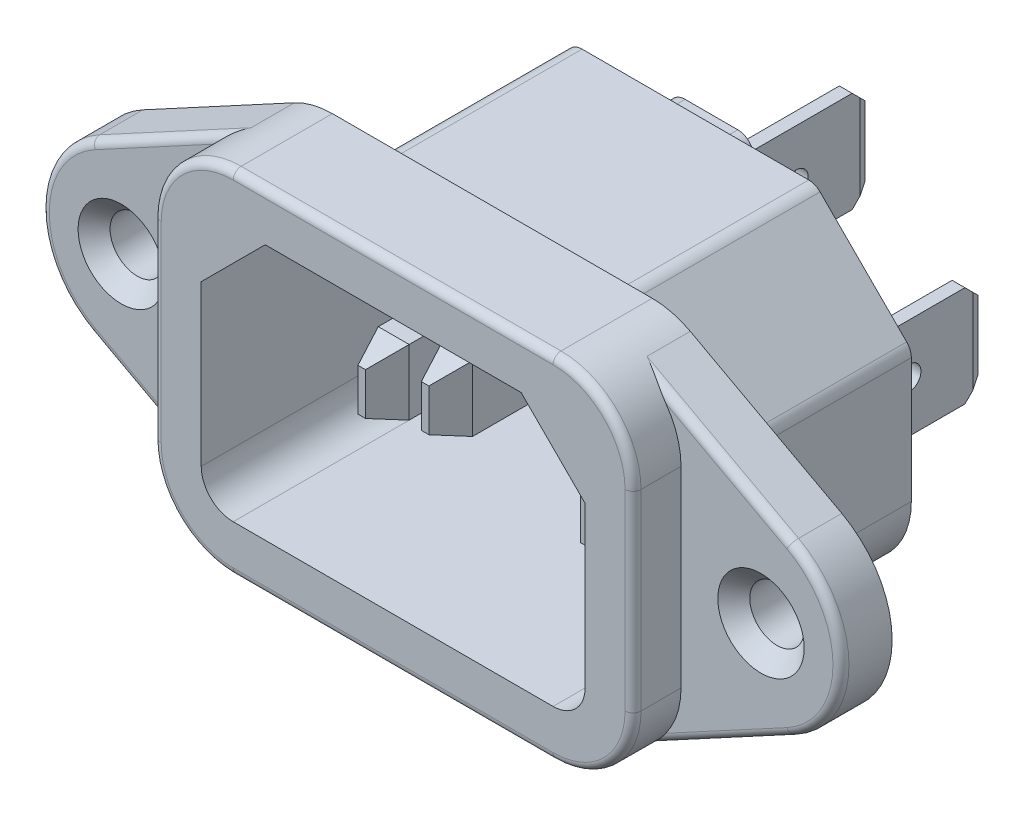
SolidWorks part; units mm, degrees
ref_plane "Front Plane" through (0, 0, 0) normal (0, 0, 1) x (1, 0, 0)
ref_plane "Top Plane" through (0, 0, 0) normal (0, 1, 0) x (1, 0, 0)
ref_plane "Right Plane" through (0, 0, 0) normal (1, 0, 0) x (0, 0, -1)
sketch "Sketch1" plane through (0, 0, 0) normal (0, 0, 1) x (1, 0, 0)
  line L0 (0, 11) -> (-10, 11)
  line L1 (-12.377, 10.3988) -> (-21.8524, 5.2786)
  line L2 (-21.8524, -5.2786) -> (-12.377, -10.3988)
  line L3 (-10, -11) -> (0, -11)
  line L4 (0, 11) -> (0, -11)
  line L5 (0, 0) -> (-19, 0) construction
  line L6 (-10, -11) -> (-10, 11) construction
  line L7 (-12.377, 10.3988) -> (-12.377, -10.3988) construction
  arc A0 (-10, 11) -> (-12.377, 10.3988) centre (-10, 6) ccw
  arc A1 (-10, -11) -> (-12.377, -10.3988) centre (-10, -6) cw
  arc A2 (-21.8524, 5.2786) -> (-21.8524, -5.2786) centre (-19, 0) ccw
  circle A3 centre (-20, 0) radius 1.7
  point P2 (0, 0)
  point P16 (-25, 0)
  dimension "D2" = 5
  dimension "D3" = 6
  dimension "D4" = 3.4
  dimension "D5" = 20
  dimension "D6" = 25
  dimension "D1" = 22
  dimension "D7" = 10
extrude "flange" add sketch "Sketch1" along normal blind 3.2
sketch "Sketch2" plane through (0, 0, 3.2) normal (0, 0, 1) x (1, 0, 0)
  line L1 (0, 11) -> (-10, 11)
  line L2 (0, 11) -> (-10, 11) construction
  line L3 (0, -11) -> (0, 11) construction
  line L4 (-15, 6) -> (-15, -6)
  line L5 (-10, -11) -> (0, -11)
  line L6 (-10, -11) -> (0, -11) construction
  arc A0 (-10, 11) -> (-15, 6) centre (-10, 6) ccw
  arc A2 (-10, -11) -> (-15, -6) centre (-10, -6) cw
  line M1 (0, -11) -> (0, 11)
  line M2 (0, 11) -> (-10, 11)
  line M8 (-10, -11) -> (0, -11)
  dimension "D1" = 5
  dimension "D2" = 15
extrude "top" add sketch "Sketch2" along normal blind 3 contours A2 A0 L4 M8 M1 M2 region at (-7.2855, 0, 3.2)
sketch "Sketch4" plane through (0, 0, 0) normal (0, 0, -1) x (-1, 0, 0)
  line L0 (0, -9.6) -> (8.5, -9.6)
  line L1 (0, -11) -> (0, 11) construction
  line L2 (13.5, -4.6) -> (13.5, 3.1858)
  line L3 (7.0858, 9.6) -> (0, 9.6)
  line L4 (13.2071, 3.8929) -> (7.7929, 9.3071)
  line L5 (0, -9.6) -> (0, 9.6)
  arc A0 (8.5, -9.6) -> (13.5, -4.6) centre (8.5, -4.6) ccw
  arc A1 (7.7929, 9.3071) -> (7.0858, 9.6) centre (7.0858, 8.6) ccw
  arc A2 (13.5, 3.1858) -> (13.2071, 3.8929) centre (12.5, 3.1858) ccw
  point P4 (13.5, 9.6)
  point P10 (0, 0)
  point P14 (7.5, 9.6)
  point P17 (13.5, 3.6)
  dimension "D3" = 5
  dimension "D4" = 1
  dimension "D1" = 19.2
  dimension "D2" = 13.5
extrude "rear" add sketch "Sketch4" along normal blind 12.7
sketch "Sketch3" plane through (0, 0, 6.2) normal (0, 0, 1) x (1, 0, 0)
  line L0 (0, -8) -> (-10, -8)
  line L1 (0, -11) -> (0, 11) construction
  line L2 (-12, -6) -> (-12, 4)
  line L3 (-12, 4) -> (-8, 8)
  line L4 (-8, 8) -> (0, 8)
  line L5 (0, 8) -> (0, -8)
  line L6 (0, 8) -> (0, -8)
  arc A0 (-10, -8) -> (-12, -6) centre (-10, -6) cw
  point P9 (0, 0)
  line M3 (0, -11) -> (0, 11)
  dimension "D3" = 2
  dimension "D1" = 12
  dimension "D2" = 16
  dimension "D4" = 12
  dimension "D5" = 135
extrude "socket" cut sketch "Sketch3" against normal blind 17 contours A0 L0 L4 L3 L2 M3 region at (-5.7701, -0.2558, 6.2)
chamfer "Chamfer2" distance 1 angle 45 1 edges at (-18.3, 0, 3.2)
mirror "Mirror1" about plane through (0, 0, 0) normal (1, 0, 0) of bodies 105
sketch "Sketch5" plane through (0, 0, -10.8) normal (0, 0, 1) x (1, 0, 0)
  line L0 (-6, -1.95) -> (6, -1.95) construction
  line L1 (-7.93, 0.1) -> (-6, 0.1)
  line L2 (-7.93, 0.1) -> (-7.93, -4)
  line L3 (-7.93, -4) -> (-6, -4)
  line L4 (-6, 0.1) -> (-6, -4)
  line L5 (0, 8) -> (0, -8) construction
  line L6 (7.93, 0.1) -> (6, 0.1)
  line L7 (7.93, 0.1) -> (7.93, -4)
  line L8 (7.93, -4) -> (6, -4)
  line L9 (6, 0.1) -> (6, -4)
  line L10 (-0.965, 4.2) -> (0.965, 4.2)
  line L11 (-0.965, 4.2) -> (-0.965, 0.1)
  line L12 (-0.965, 0.1) -> (0.965, 0.1)
  line L13 (0.965, 4.2) -> (0.965, 0.1)
  line L14 (-8, 8) -> (8, 8) construction
  line L15 (10, -8) -> (-10, -8) construction
  point P20 (0, -1.95)
  point P21 (0, 0.1)
  dimension "D1" = 1.93
  dimension "D2" = 4.1
  dimension "D3" = 12
  dimension "D4" = 6.05
extrude "pin" add sketch "Sketch5" along normal blind 12
sketch "Sketch6" plane through (0, 0, 1.2) normal (0, 0, 1) x (1, 0, 0)
  line L4 (-0.965, 4.2) -> (-0.965, 0.1)
  line L5 (-0.965, 0.1) -> (0.965, 0.1)
  line L6 (0.965, 0.1) -> (0.965, 4.2)
  line L7 (0.965, 4.2) -> (-0.965, 4.2)
  line L8 (-0.965, 4.2) -> (-0.965, 0.1)
  line L9 (-0.965, 0.1) -> (0.965, 0.1)
  line L10 (0.965, 0.1) -> (0.965, 4.2)
  line L11 (0.965, 4.2) -> (-0.965, 4.2)
  dimension "D1" = 0
extrude "pinGnd" add sketch "Sketch6" along normal blind 3
chamfer "Chamfer1" distance 2 angle 20 12 edges at (6.965, 0.1, 1.2) (7.93, -1.95, 1.2) (6.965, -4, 1.2) (6, -1.95, 1.2) (-6.965, 0.1, 1.2) (-7.93, -1.95, 1.2) (-6.965, -4, 1.2) (-6, -1.95, 1.2) (0, 4.2, 4.2) (0.965, 2.15, 4.2) (0, 0.1, 4.2) (-0.965, 2.15, 4.2) first distance on face at (6.965, 0.1, -4.8) first distance on face at (7.93, -1.95, -4.8) first distance on face at (6.965, -4, -4.8) first distance on face at (6, -1.95, -4.8) first distance on face at (-6.965, 0.1, -4.8) first distance on face at (-7.93, -1.95, -4.8) first distance on face at (-6.965, -4, -4.8) first distance on face at (-6, -1.95, -4.8) first distance on face at (0, 4.2, -3.3) first distance on face at (0.965, 2.15, -3.3) first distance on face at (0, 0.1, -3.3) first distance on face at (-0.965, 2.15, -3.3)
sketch "Sketch8" plane through (0, 0, -12.7) normal (0, 0, -1) x (-1, 0, 0)
  line L0 (-8.5, -9.6) -> (8.5, -9.6) construction
  line L1 (-8.7, 2.1) -> (-5.4, 2.1)
  line L2 (-9.7, 1.1) -> (-9.7, -8.1)
  line L3 (-8.7, -9.1) -> (-5.4, -9.1)
  line L4 (-4.4, 1.1) -> (-4.4, -8.1)
  arc A0 (-8.7, 2.1) -> (-9.7, 1.1) centre (-8.7, 1.1) ccw
  arc A1 (-4.4, 1.1) -> (-5.4, 2.1) centre (-5.4, 1.1) ccw
  arc A2 (-5.4, -9.1) -> (-4.4, -8.1) centre (-5.4, -8.1) ccw
  arc A3 (-9.7, -8.1) -> (-8.7, -9.1) centre (-8.7, -8.1) ccw
  point P14 (0, -9.6)
  dimension "D1" = 1
  dimension "D2" = 5.3
  dimension "D3" = 11.2
  dimension "D4" = 0.5
  dimension "D5" = 4.4
extrude "Extrude8" add sketch "Sketch8" along normal blind 1
sketch "Sketch9" plane through (0, 0, -12.7) normal (0, 0, -1) x (-1, 0, 0)
  line L0 (-4.4, -8.1) -> (-4.4, 1.1) construction
  line L2 (7.0858, 9.6) -> (-7.0858, 9.6) construction
  point P0 (0, 3.5)
  point P1 (7.05, -3.5)
  point P5 (-4.4, -3.5)
  dimension "D1" = 11.45
  dimension "D2" = 0
  dimension "D3" = 6.1
pattern_sketch "Sketch-Pattern1" of "Extrude8" driven by "Sketch9"
sketch "Sketch10" plane through (0, 0, -13.7) normal (0, 0, -1) x (-1, 0, 0)
  line L0 (7.05, 2.1) -> (7.05, -9.1) construction
  line L1 (0, 6.65) -> (-0.8, 6.65)
  line L2 (0, 6.65) -> (0, 0.35)
  line L3 (0, 0.35) -> (-0.8, 0.35)
  line L4 (-0.8, 6.65) -> (-0.8, 0.35)
  line L5 (7.05, -0.35) -> (6.25, -0.35)
  line L6 (7.05, -0.35) -> (7.05, -6.65)
  line L7 (7.05, -6.65) -> (6.25, -6.65)
  line L8 (6.25, -0.35) -> (6.25, -6.65)
  line L9 (-7.05, -0.35) -> (-7.85, -0.35)
  line L10 (-7.05, -0.35) -> (-7.05, -6.65)
  line L11 (-7.05, -6.65) -> (-7.85, -6.65)
  line L12 (-7.85, -0.35) -> (-7.85, -6.65)
  line L14 (8.7, 2.1) -> (5.4, 2.1) construction
  line L15 (5.4, -9.1) -> (8.7, -9.1) construction
  line L16 (-7.05, 2.1) -> (-7.05, -9.1) construction
  line L17 (-5.4, 2.1) -> (-8.7, 2.1) construction
  line L18 (-8.7, -9.1) -> (-5.4, -9.1) construction
  line L19 (0, 9.1) -> (0, -2.1) construction
  line L20 (1.65, 9.1) -> (-1.65, 9.1) construction
  line L21 (-1.65, -2.1) -> (1.65, -2.1) construction
  point P18 (7.05, -3.5)
  point P25 (-7.05, -3.5)
  point P32 (0, 3.5)
  dimension "D1" = 0.8
  dimension "D2" = 6.3
extrude "rear_blades" add sketch "Sketch10" along normal blind 9
chamfer "blade_chmf" distance 1 angle 45 6 edges at (-6.65, -0.35, -22.7) (-6.65, -6.65, -22.7) (0.4, 6.65, -22.7) (0.4, 0.35, -22.7) (7.45, -0.35, -22.7) (7.45, -6.65, -22.7)
chamfer "blade_chmf2" distance 0.5 angle 20 6 edges at (-7.05, -3.5, -22.7) (-6.25, -3.5, -22.7) (7.85, -3.5, -22.7) (7.05, -3.5, -22.7) (0.8, 3.5, -22.7) (0, 3.5, -22.7) first distance on face at (-7.05, -3.5, -19.3667) first distance on face at (-6.25, -3.5, -19.3667) first distance on face at (7.85, -3.5, -19.3667) first distance on face at (7.05, -3.5, -19.3667) first distance on face at (0.8, 3.5, -19.3667) first distance on face at (0, 3.5, -19.3667)
fillet "Fillet1" radius 0.5 9 edges at (25, 0, 3.2) (-25, 0, 3.2) (-13.5355, -9.5355, 6.2) (-15, 0, 6.2) (-13.5355, 9.5355, 6.2)
sketch "Sketch11" plane through (-7.05, 0, 0) normal (-1, 0, 0) x (0, 0, 1)
  line L0 (-22.2, -3.5) -> (-18.95, -3.5) construction
  line L1 (-22.2, -0.85) -> (-22.2, -6.15) construction
  line L2 (-18.2, -3.5) -> (-18.2, 3.5) construction
  line L3 (-22.2, 6.15) -> (-22.2, 0.85) construction
  line L4 (-22.2, 6.15) -> (-22.2, 0.85)
  line L5 (-22.2, 3.5) -> (-18.2, 3.5) construction
  circle A0 centre (-18.2, -3.5) radius 0.75
  circle A1 centre (-18.2, 3.5) radius 0.75
  point P6 (-18.95, -3.5)
  dimension "D1" = 1.5
  dimension "D2" = 3.25
extrude "Extrude9" cut sketch "Sketch11" against normal through all contours A0 | A1 region at (-7.05, -3.5, -18.2) region at (-7.05, 3.5, -18.2)
